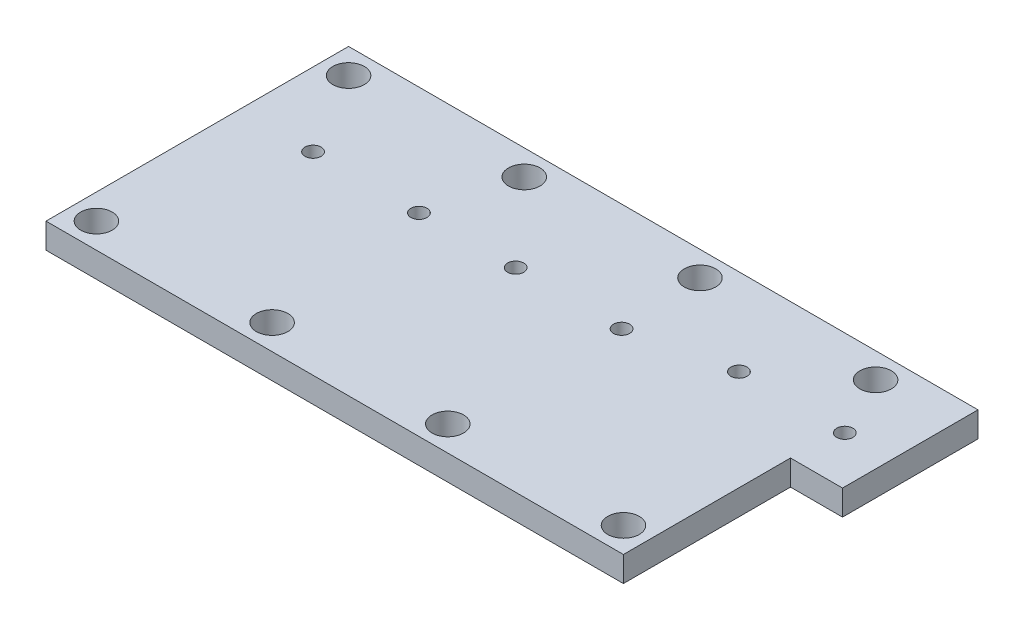
SolidWorks part; units mm, degrees
material "K110"
ref_plane "Front Plane" through (0, 0, 0) normal (0, 0, 1) x (1, 0, 0)
ref_plane "Top Plane" through (0, 0, 0) normal (0, 1, 0) x (1, 0, 0)
ref_plane "Right Plane" through (0, 0, 0) normal (1, 0, 0) x (0, 0, -1)
sketch "Sketch1" plane through (0, 0, 0) normal (0, 1, 0) x (1, 0, 0)
  line L0 (-229, 15.28) -> (-229, 9.28) construction
  line L1 (-229, -60) -> (0, -60)
  line L2 (-229, -60) -> (-229, 60)
  line L3 (-229, 60) -> (0, 60)
  line L4 (0, -60) -> (0, 60)
  point P0 (0, 0)
  dimension "D1" = 120
  dimension "D2" = 229
extrude "Boss-Extrude1" add sketch "Sketch1" against normal blind 10
sketch "Sketch2" plane through (0, 0, 0) normal (0, 1, 0) x (1, 0, 0)
  line L0 (21.6325, 5.27) -> (21.6325, 60) construction
  line L1 (0, 60) -> (20.6325, 60)
  line L2 (0, 60) -> (0, 6.27)
  line L3 (0, 6.27) -> (20.6325, 6.27)
  line L4 (20.6325, 60) -> (20.6325, 6.27)
  line L5 (1, 5.27) -> (21.6325, 5.27) construction
  dimension "D1" = 1
  dimension "D2" = 1
extrude "Boss-Extrude2" add sketch "Sketch2" against normal up to surface (10 mm away) up to face at (-114.5, -10, 0)
hole_wizard "Ø12.5 (12.5) Diameter Hole1" positions "Sketch5" profile "Sketch4" hole size "Ø12.5" standard "ISO" end condition through all
sketch "Sketch5" plane through (0, -10, 0) normal (0, -1, 0) x (-1, 0, 0)
  line L0 (80.2527, 48.6977) -> (79.3713, 51.6698) construction
  point P0 (9.969, 50)
  point P3 (79.812, 50.1838)
  point P7 (149.323, 50)
  point P10 (219, 50)
  point P13 (219, -50)
  point P16 (149.323, -50)
  point P19 (79.646, -50)
  point P22 (9.969, -50)
sketch "Sketch4" plane through (-9.969, -10, -50) normal (1, 0, 0) x (0, 0, -1)
  line L0 (0, 0) -> (0, 10)
  line L1 (0, 10) -> (6.25, 10)
  line L2 (6.25, 10) -> (6.25, 0)
  line L5 (6.25, 0) -> (0, 0)
  line L11 (0, -6.35) -> (0, 107.95) construction
  dimension "Thru Hole Dia." = 12.5
  dimension "Thru Hole Depth" = 10
hole_wizard "M6 Clearance Hole1" positions "Sketch8" profile "Sketch7" hole size "M6" standard "ISO" end condition through all
sketch "Sketch8" plane through (0, -10, 0) normal (0, -1, 0) x (-1, 0, 0)
  point P0 (-2.125, 25.691)
  point P3 (39.875, 25.691)
  point P6 (77.875, 17.1524)
  point P9 (119.875, 17.1524)
  point P12 (157.875, 16.78)
  point P15 (199.875, 16.78)
sketch "Sketch7" plane through (2.125, -10, -25.691) normal (1, 0, 0) x (0, 0, -1)
  line L0 (0, 0) -> (0, 10)
  line L1 (0, 10) -> (3.2, 10)
  line L2 (3.2, 10) -> (3.2, 0)
  line L5 (3.2, 0) -> (0, 0)
  line L11 (0, -6.35) -> (0, 107.95) construction
  dimension "Thru Hole Dia." = 6.4
  dimension "Thru Hole Depth" = 10
